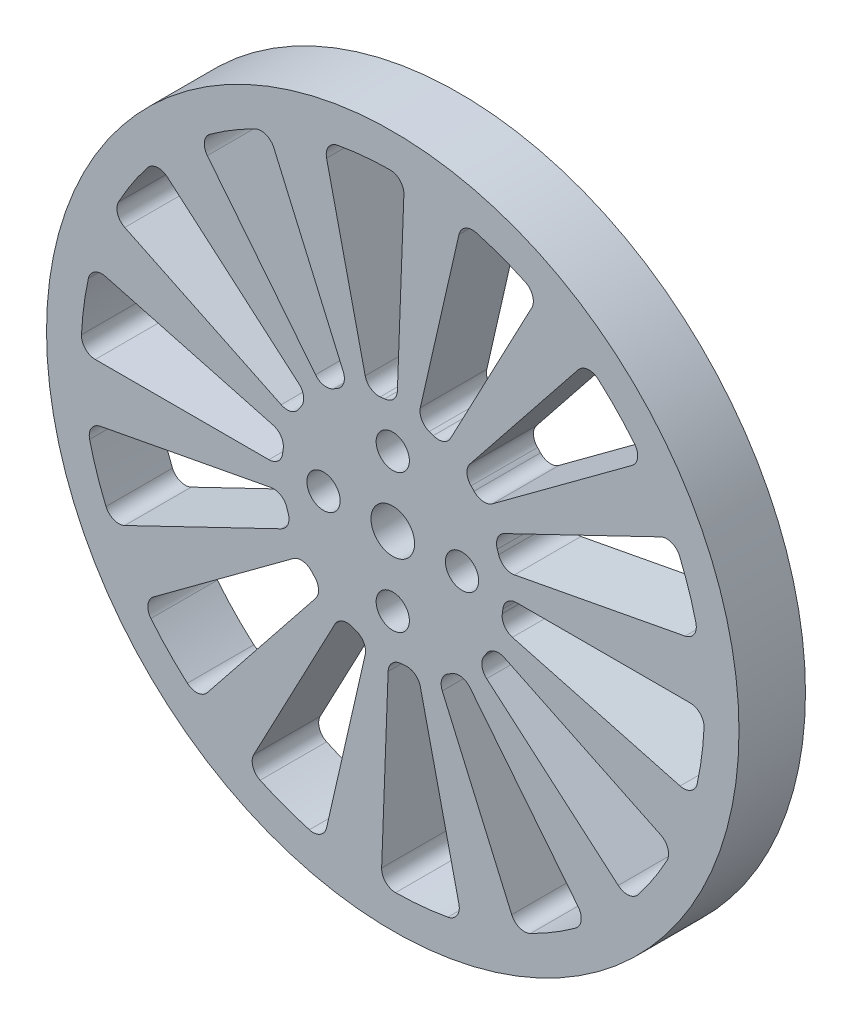
SolidWorks part; units mm, degrees
ref_plane "Front Plane" through (0, 0, 0) normal (0, 0, 1) x (1, 0, 0)
ref_plane "Top Plane" through (0, 0, 0) normal (0, 1, 0) x (1, 0, 0)
ref_plane "Right Plane" through (0, 0, 0) normal (1, 0, 0) x (0, 0, -1)
sketch "Sketch1" plane through (0, 0, 0) normal (0, 0, 1) x (1, 0, 0)
  circle A0 centre (0, 0) radius 31.75
  circle A1 centre (0, 6.35) radius 1.524
  circle A2 centre (6.35, 0) radius 1.524
  circle A3 centre (0, -6.35) radius 1.524
  circle A4 centre (-6.35, 0) radius 1.524
  circle A5 centre (0, 0) radius 2
  point P14 (0, 0)
  dimension "D1" = 63.5
  dimension "D2" = 3.048
  dimension "D4" = 4
  dimension "D5" = 4
  dimension "D3" = 6.35
extrude "Boss-Extrude1" add sketch "Sketch1" along normal blind 6.096
sketch "Sketch2" plane through (0, 0, 6.096) normal (0, 0, 1) x (1, 0, 0)
  line L0 (-27.2754, 0) -> (-11.3592, 0)
  line L1 (-26.3461, 7.0594) -> (-10.9722, 2.94)
  arc A0 (-27.9154, 6.104) -> (-28.5441, 1.3291) centre (0, 0) ccw
  arc A1 (-10.0452, 1.5229) -> (-10.0971, 1.1289) centre (0, 0) ccw
  arc A2 (-11.3592, 0) -> (-10.0971, 1.1289) centre (-11.3592, 1.27) ccw
  arc A3 (-10.9722, 2.94) -> (-10.0452, 1.5229) centre (-11.3009, 1.7133) cw
  arc A4 (-28.5441, 1.3291) -> (-27.2754, 0) centre (-27.2754, 1.27) ccw
  arc A5 (-27.9154, 6.104) -> (-26.3461, 7.0594) centre (-26.6748, 5.8327) cw
  point P8 (-10.16, 0)
  dimension "D1" = 28.575
  dimension "D3" = 1.27
  dimension "D4" = 10.16
  dimension "D2" = 15
extrude "Cut-Extrude1" cut sketch "Sketch2" against normal up to next
ref_axis "Axis1" through (0, 0, 6.096) along (0, 0, -1)
pattern_circular "CirPattern1" count 14 over 360 about axis through (0, 0, 6.096) along (0, 0, -1) of "Cut-Extrude1"
